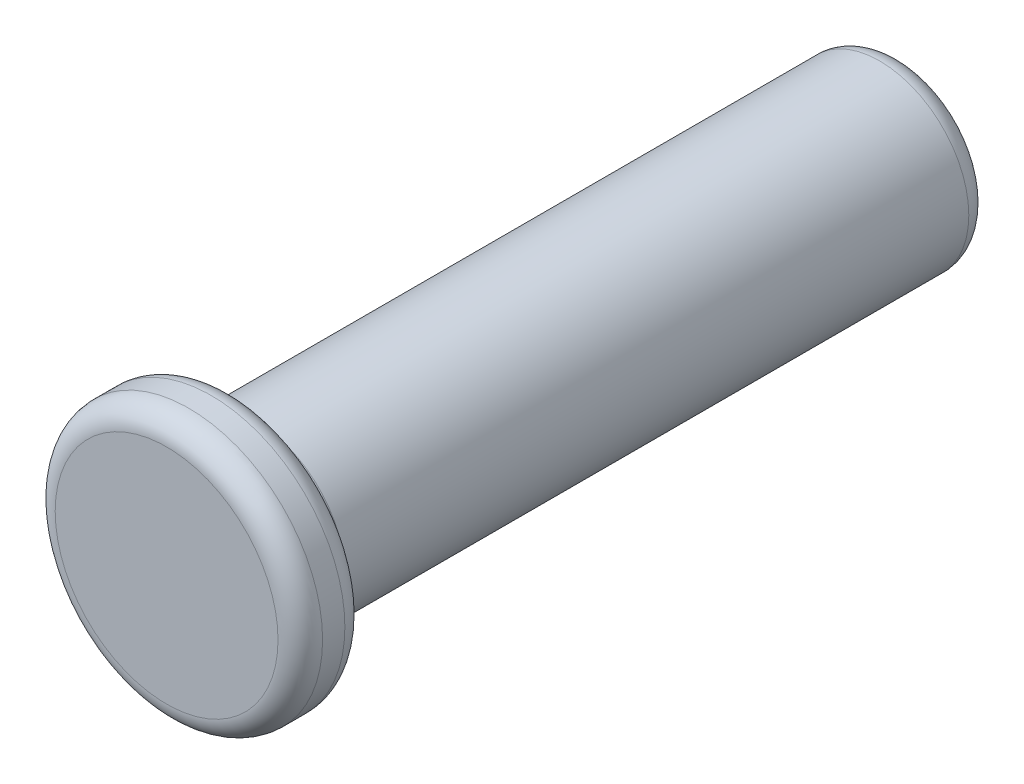
SolidWorks part; units mm, degrees
ref_plane "Front Plane" through (0, 0, 0) normal (0, 0, 1) x (1, 0, 0)
ref_plane "Top Plane" through (0, 0, 0) normal (0, 1, 0) x (1, 0, 0)
ref_plane "Right Plane" through (0, 0, 0) normal (1, 0, 0) x (0, 0, -1)
sketch "Sketch1" plane through (0, 0, 0) normal (0, 0, 1) x (1, 0, 0)
  circle A0 centre (0, 0) radius 4
  dimension "D1" = 8
extrude "Boss-Extrude1" add sketch "Sketch1" along normal mid plane 30
sketch "Sketch2" plane through (0, 0, 15) normal (0, 0, 1) x (1, 0, 0)
  circle A0 centre (0, 0) radius 6
  dimension "D1" = 12
extrude "Boss-Extrude2" add sketch "Sketch2" along normal blind 3
fillet "Fillet1" radius 1 4 edges at (6, 0, 18) (6, 0, 15) (4, 0, 15) (4, 0, -15)
